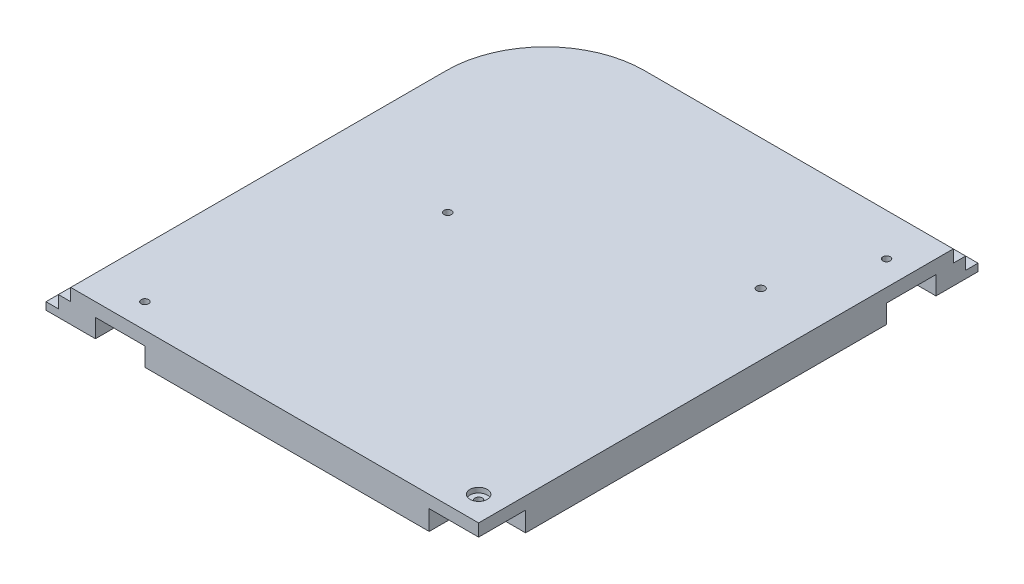
SolidWorks part; units mm, degrees
material "PETG"
ref_plane "Alzado" through (0, 0, 0) normal (0, 0, 1) x (1, 0, 0)
ref_plane "Planta" through (0, 0, 0) normal (0, 1, 0) x (1, 0, 0)
ref_plane "Vista lateral" through (0, 0, 0) normal (1, 0, 0) x (0, 0, -1)
sketch "Croquis1" plane through (0, 0, 0) normal (0, 1, 0) x (1, 0, 0)
  line L1 (125, 225) -> (-125, 225)
  line L2 (175, 175) -> (175, -175)
  line L3 (125, -225) -> (-125, -225)
  line L4 (-175, 175) -> (-175, -175)
  line L5 (175, 225) -> (-175, -225) construction
  line L6 (175, -225) -> (-175, 225) construction
  arc A0 (-125, -225) -> (-175, -175) centre (-125, -175) cw
  arc A1 (175, -175) -> (125, -225) centre (125, -175) cw
  arc A2 (125, 225) -> (175, 175) centre (125, 175) cw
  arc A3 (-125, 225) -> (-175, 175) centre (-125, 175) ccw
  point P0 (0, 0)
  dimension "D3" = 50
  dimension "D1" = 450
  dimension "D2" = 350
extrude "Saliente-Extruir1" add sketch "Croquis1" along normal blind 3
sketch "Croquis2" plane through (0, 3, 0) normal (0, 1, 0) x (1, 0, 0)
  line L8 (-125, -220) -> (125, -220)
  line L9 (170, -175) -> (170, 175)
  line L10 (125, 220) -> (-125, 220)
  line L11 (-170, 175) -> (-170, -175)
  line L12 (-125, -220) -> (125, -220)
  line L13 (170, -175) -> (170, 175)
  line L14 (125, 220) -> (-125, 220)
  line L15 (-170, 175) -> (-170, -175)
  arc A8 (-170, -175) -> (-125, -220) centre (-125, -175) ccw
  arc A9 (125, -220) -> (170, -175) centre (125, -175) ccw
  arc A10 (170, 175) -> (125, 220) centre (125, 175) ccw
  arc A11 (-125, 220) -> (-170, 175) centre (-125, 175) ccw
  arc A12 (-170, -175) -> (-125, -220) centre (-125, -175) ccw
  arc A13 (125, -220) -> (170, -175) centre (125, -175) ccw
  arc A14 (170, 175) -> (125, 220) centre (125, 175) ccw
  arc A15 (-125, 220) -> (-170, 175) centre (-125, 175) ccw
  dimension "D1" = 5
extrude "Saliente-Extruir2" add sketch "Croquis2" along normal blind 5
sketch "Croquis3" plane through (0, 8, 0) normal (0, 1, 0) x (1, 0, 0)
  line L8 (-125, -215) -> (125, -215)
  line L9 (165, -175) -> (165, 175)
  line L10 (125, 215) -> (-125, 215)
  line L11 (-165, 175) -> (-165, -175)
  line L12 (-125, -215) -> (125, -215)
  line L13 (165, -175) -> (165, 175)
  line L14 (125, 215) -> (-125, 215)
  line L15 (-165, 175) -> (-165, -175)
  arc A8 (-165, -175) -> (-125, -215) centre (-125, -175) ccw
  arc A9 (125, -215) -> (165, -175) centre (125, -175) ccw
  arc A10 (165, 175) -> (125, 215) centre (125, 175) ccw
  arc A11 (-125, 215) -> (-165, 175) centre (-125, 175) ccw
  arc A12 (-165, -175) -> (-125, -215) centre (-125, -175) ccw
  arc A13 (125, -215) -> (165, -175) centre (125, -175) ccw
  arc A14 (165, 175) -> (125, 215) centre (125, 175) ccw
  arc A15 (-125, 215) -> (-165, 175) centre (-125, 175) ccw
  dimension "D1" = 5
extrude "Saliente-Extruir3" add sketch "Croquis3" along normal blind 5
sketch "Croquis6" plane through (0, 13, 0) normal (0, 1, 0) x (1, 0, 0)
  line L0 (0, 0) -> (0, -215) construction
  line L1 (-125, -215) -> (125, -215) construction
  circle A0 centre (-87, -130) radius 2.25
  circle A1 centre (-87, -70) radius 2.25
  circle A2 centre (-87, -10) radius 2.25
  circle A3 centre (87, -130) radius 2.25
  circle A4 centre (87, -70) radius 2.25
  circle A5 centre (87, -10) radius 2.25
  dimension "D1" = 4.5
  dimension "D2" = 4.5
  dimension "D3" = 4.5
  dimension "D4" = 87
  dimension "D5" = 60
  dimension "D6" = 60
  dimension "D7" = 10
extrude "Cortar-Extruir3" cut sketch "Croquis6" against normal blind 5
sketch "Croquis7" plane through (0, 13, 0) normal (0, 1, 0) x (1, 0, 0)
  line L0 (0, -11.4875) -> (0, -220) construction
  line L1 (-125, -220) -> (125, -220) construction
  circle A0 centre (-115, -70) radius 1.5
  circle A1 centre (-115, 125.5) radius 1.5
  circle A2 centre (115, -70) radius 1.5
  circle A3 centre (115, 125.5) radius 1.5
  dimension "D1" = 3
  dimension "D2" = 3
  dimension "D3" = 115
  dimension "D4" = 70
  dimension "D5" = 125.5
  dimension "D6" = 115
extrude "Cortar-Extruir4" cut sketch "Croquis7" against normal through all
sketch "Croquis8" plane through (0, 13, 0) normal (0, 1, 0) x (1, 0, 0)
  line L0 (13.0147, -158) -> (13.0147, -178) construction
  line L4 (16.0147, -158) -> (16.0147, -178)
  line L5 (10.0147, -158) -> (10.0147, -178)
  line L6 (25.0147, -158) -> (25.0147, -178) construction
  line L7 (28.0147, -158) -> (28.0147, -178)
  line L8 (22.0147, -158) -> (22.0147, -178)
  line L9 (25.0147, -106) -> (25.0147, -126) construction
  line L10 (28.0147, -106) -> (28.0147, -126)
  line L11 (22.0147, -106) -> (22.0147, -126)
  line L12 (13.0147, -106) -> (13.0147, -126) construction
  line L15 (16.0147, -106) -> (16.0147, -126)
  line L16 (10.0147, -106) -> (10.0147, -126)
  arc A0 (10.0147, -168) -> (13.0147, -171) centre (13.0147, -168) ccw construction
  arc A1 (25.0147, -171) -> (28.0147, -168) centre (25.0147, -168) ccw construction
  arc A2 (16.0147, -116) -> (13.0147, -113) centre (13.0147, -116) ccw construction
  arc A3 (22.0147, -116) -> (25.0147, -119) centre (25.0147, -116) ccw construction
  arc A6 (16.0147, -158) -> (10.0147, -158) centre (13.0147, -158) ccw
  arc A7 (10.0147, -178) -> (16.0147, -178) centre (13.0147, -178) ccw
  arc A8 (28.0147, -158) -> (22.0147, -158) centre (25.0147, -158) ccw
  arc A9 (22.0147, -178) -> (28.0147, -178) centre (25.0147, -178) ccw
  arc A10 (28.0147, -106) -> (22.0147, -106) centre (25.0147, -106) ccw
  arc A11 (22.0147, -126) -> (28.0147, -126) centre (25.0147, -126) ccw
  arc A14 (16.0147, -106) -> (10.0147, -106) centre (13.0147, -106) ccw
  arc A15 (10.0147, -126) -> (16.0147, -126) centre (13.0147, -126) ccw
  arc A16 (13.0147, -113) -> (10.0147, -116) centre (13.0147, -116) ccw construction
  arc A17 (10.0147, -116) -> (13.0147, -119) centre (13.0147, -116) ccw construction
  arc A18 (13.0147, -119) -> (16.0147, -116) centre (13.0147, -116) ccw construction
  arc A19 (28.0147, -116) -> (25.0147, -113) centre (25.0147, -116) ccw construction
  arc A20 (25.0147, -119) -> (28.0147, -116) centre (25.0147, -116) ccw construction
  arc A21 (25.0147, -113) -> (22.0147, -116) centre (25.0147, -116) ccw construction
  arc A22 (25.0147, -165) -> (22.0147, -168) centre (25.0147, -168) ccw construction
  arc A23 (22.0147, -168) -> (25.0147, -171) centre (25.0147, -168) ccw construction
  arc A24 (28.0147, -168) -> (25.0147, -165) centre (25.0147, -168) ccw construction
  arc A25 (16.0147, -168) -> (13.0147, -165) centre (13.0147, -168) ccw construction
  arc A26 (13.0147, -171) -> (16.0147, -168) centre (13.0147, -168) ccw construction
  arc A27 (13.0147, -165) -> (10.0147, -168) centre (13.0147, -168) ccw construction
  point P10 (13.0147, -168)
  point P16 (25.0147, -168)
  point P23 (25.0147, -116)
  point P32 (13.0147, -116)
  dimension "D1" = 6
  dimension "D2" = 6
  dimension "D3" = 6
  dimension "D4" = 6
  dimension "D5" = 12
  dimension "D6" = 52
  dimension "D7" = 116
  dimension "D8" = 13.0147
  dimension "D9" = 20
  dimension "D10" = 20
  dimension "D11" = 20
  dimension "D12" = 20
extrude "Cortar-Extruir5" cut sketch "Croquis8" against normal blind 8
sketch "Croquis9" plane through (0, 13, 0) normal (0, 1, 0) x (1, 0, 0)
  circle A0 centre (13.0147, -168) radius 1.5
  circle A1 centre (25.0147, -168) radius 1.5
  circle A2 centre (13.0147, -116) radius 1.5
  circle A3 centre (25.0147, -116) radius 1.5
  circle A4 centre (-87, -70) radius 2.25 construction
  circle A5 centre (-87, -130) radius 1.5
  circle A6 centre (-87, -70) radius 1.5
  circle A7 centre (-87, -10) radius 1.5
  circle A8 centre (87, -10) radius 1.5
  circle A9 centre (87, -70) radius 1.5
  circle A10 centre (87, -130) radius 1.5
  dimension "D1" = 3
  dimension "D2" = 3
  dimension "D3" = 3
  dimension "D4" = 3
  dimension "D5" = 100.0147
  dimension "D6" = 112.0147
  dimension "D7" = 46
  dimension "D8" = 98
extrude "Cortar-Extruir6" cut sketch "Croquis9" against normal through all
sketch "Croquis10" plane through (0, 13, 0) normal (0, 1, 0) x (1, 0, 0)
  line L1 (50, -120) -> (75, -120)
  line L2 (50, -120) -> (50, -170)
  line L3 (50, -170) -> (75, -170)
  line L4 (75, -120) -> (75, -170)
  dimension "D1" = 50
  dimension "D2" = 25
  dimension "D3" = 120
  dimension "D4" = 50
extrude "Cortar-Extruir7" cut sketch "Croquis10" against normal blind 5
chamfer "Chaflán1" distance 5 angle 45 4 edges at (62.5, 13, 120) (50, 13, 145) (62.5, 13, 170) (75, 13, 145)
sketch "Croquis13" plane through (0, 13, 0) normal (0, 1, 0) x (1, 0, 0)
  circle A0 centre (-60, -50) radius 2.25
  circle A1 centre (-20, -50) radius 2.25
  circle A2 centre (-20, -90) radius 2.25
  circle A3 centre (-60, -90) radius 2.25
  circle A4 centre (-20, -50) radius 3.5
  circle A5 centre (-60, -50) radius 3.5
  circle A6 centre (-60, -90) radius 3.5
  circle A7 centre (-20, -90) radius 3.5
  dimension "D1" = 4.5
  dimension "D2" = 40
  dimension "D6" = 7
  dimension "D3" = 40
  dimension "D4" = 20
  dimension "D5" = 50
extrude "Saliente-Extruir4" add sketch "Croquis13" along normal blind 25
sketch "Croquis14" plane through (0, 13, 0) normal (0, 1, 0) x (1, 0, 0)
  circle A0 centre (3.15, -40) radius 1.25
  circle A1 centre (67.55, -40) radius 1.25
  circle A3 centre (67.55, -40) radius 3
  circle A4 centre (3.15, -40) radius 3
  circle A5 centre (3, -91.9) radius 3
  circle A6 centre (3, -91.9) radius 1.25
  circle A7 centre (67.4, -91.9) radius 3
  circle A8 centre (67.4, -91.9) radius 1.25
  circle A9 centre (-10, -102.9) radius 1.5
  circle A10 centre (-10, -102.9) radius 3
  circle A11 centre (-10, -118.1085) radius 3
  circle A12 centre (-10, -118.1085) radius 1.5
  dimension "D1" = 2.5
  dimension "D2" = 6
  dimension "D7" = 3
  dimension "D8" = 6
  dimension "D9" = 6
  dimension "D10" = 3
  dimension "D3" = 51.9
  dimension "D4" = 64.4
  dimension "D5" = 40
  dimension "D6" = 3
  dimension "D11" = 11
  dimension "D12" = 13
  dimension "D13" = 15.2085
  dimension "D14" = 64.4
  dimension "D15" = 0.15
extrude "Saliente-Extruir5" add sketch "Croquis14" along normal blind 10
sketch "Croquis12" plane through (0, 13, 0) normal (0, 1, 0) x (1, 0, 0)
  line L0 (-25.1, 12) -> (-25.1, 13.6) construction
  line L1 (-25.1, 12) -> (-23.5, 12) construction
  line L2 (25.1, 12) -> (23.5, 12) construction
  line L3 (25.1, 12) -> (25.1, 13.6) construction
  line L4 (25.1, 162.2) -> (25.1, 160.6) construction
  line L5 (25.1, 162.2) -> (23.5, 162.2) construction
  line L6 (-25.1, 162.2) -> (-23.5, 162.2) construction
  line L7 (-25.1, 162.2) -> (-25.1, 160.6) construction
  circle A0 centre (-25.1, 162.2) radius 1.6
  circle A1 centre (25.1, 162.2) radius 1.6
  circle A2 centre (-25.1, 12) radius 1.6
  circle A3 centre (25.1, 12) radius 1.6
  dimension "D4" = 3.2
  dimension "D1" = 12
  dimension "D2" = 47
  dimension "D3" = 23.5
  dimension "D5" = 147
  dimension "D6" = 147
extrude "Cortar-Extruir9" cut sketch "Croquis12" against normal through all
sketch "Croquis11" plane through (0, 0, 0) normal (0, -1, 0) x (1, 0, 0)
  line L0 (13.0147, 168) -> (25.0147, 168) construction
  line L1 (13.0147, 188) -> (25.0147, 188)
  line L2 (13.0147, 148) -> (25.0147, 148)
  line L3 (13.0147, 116) -> (25.0147, 116) construction
  line L4 (13.0147, 136) -> (25.0147, 136)
  line L5 (13.0147, 96) -> (25.0147, 96)
  circle A4 centre (87, 130) radius 6
  circle A5 centre (87, 70) radius 6
  circle A6 centre (87, 10) radius 6
  circle A7 centre (-87, 10) radius 6
  circle A8 centre (-87, 70) radius 6
  circle A9 centre (-87, 130) radius 6
  circle A10 centre (-115, 70) radius 6
  circle A11 centre (115, 70) radius 6
  circle A12 centre (115, -125.5) radius 6
  circle A15 centre (-115, -125.5) radius 6
  arc A16 (13.0147, 188) -> (13.0147, 148) centre (13.0147, 168) ccw
  arc A17 (25.0147, 148) -> (25.0147, 188) centre (25.0147, 168) ccw
  circle A18 centre (-25.1, -162.2) radius 6
  arc A19 (13.0147, 136) -> (13.0147, 96) centre (13.0147, 116) ccw
  arc A20 (25.0147, 96) -> (25.0147, 136) centre (25.0147, 116) ccw
  circle A21 centre (25.1, -162.2) radius 6
  circle A22 centre (-25.1, -12) radius 6
  circle A23 centre (25.1, -12) radius 6
  point P3 (19.0147, 168)
  point P10 (19.0147, 116)
  dimension "D1" = 12
  dimension "D2" = 20
  dimension "D3" = 20
extrude "Cortar-Extruir8" cut sketch "Croquis11" against normal blind 5
sketch "Croquis16" plane through (0, 0, 0) normal (1, 0, 0) x (0, 0, -1)
  line L0 (-175, 0) -> (175, 0) construction
  line L5 (-175, 8) -> (175, 8) construction
  line L6 (2, 8) -> (42, 8)
  line L7 (2, 8) -> (2, 0)
  line L8 (2, 0) -> (42, 0)
  line L9 (42, 8) -> (42, 0)
  dimension "D1" = 40
  dimension "D2" = 2
extrude "Cortar-Extruir10" cut sketch "Croquis16" against normal mid plane 40
sketch "Croquis17" plane through (0, 13, 0) normal (0, 1, 0) x (1, 0, 0)
  line L0 (-175, 23) -> (0, 23)
  line L2 (0, 23) -> (0, -225) construction
  line L3 (-125, -225) -> (125, -225) construction
  line L4 (-175, 175) -> (-175, -175) construction
  line L5 (-175, 23) -> (-175, 225) construction
  line L6 (-175, 225) -> (0, 225) construction
  line L7 (175, 225) -> (175, 23)
  line L8 (175, -225) -> (0, -225)
  line L9 (125, 225) -> (-125, 225) construction
  line L10 (175, -175) -> (175, 175) construction
  line L11 (0, 23) -> (175, 23) construction
  line L12 (-175, 23) -> (-175, -225)
  line L13 (-175, -225) -> (0, -225)
  line L14 (175, 23) -> (175, -225)
  line L15 (0, 23) -> (0, 225)
  line L16 (0, 225) -> (175, 225)
  point P20 (0, 0)
  dimension "D1" = 248
extrude "Cortar-Extruir11" cut sketch "Croquis17" against normal mid plane 60
sketch "Croquis19" plane through (0, 13, 0) normal (0, 1, 0) x (1, 0, 0)
  line L4 (0, 225) -> (-125, 225) construction
  line L5 (0, 215) -> (0, 23) construction
  line L6 (0, 23) -> (-165, 23) construction
  line L7 (-175, 175) -> (-175, 23) construction
  circle A0 centre (-10, 33) radius 1.5
  circle A1 centre (-10, 198) radius 1.5
  circle A2 centre (-145, 33) radius 1.5
  dimension "D1" = 3
  dimension "D2" = 3
  dimension "D3" = 3
  dimension "D4" = 27
  dimension "D5" = 10
  dimension "D6" = 10
  dimension "D7" = 30
  dimension "D8" = 10
extrude "Cortar-Extruir12" cut sketch "Croquis19" against normal blind 70
sketch "Croquis20" plane through (0, 0, 0) normal (1, 0, 0) x (0, 0, -1)
  line L5 (225, 0) -> (225, 3) construction
  line L6 (188, 7.5) -> (208, 7.5)
  line L7 (188, 7.5) -> (188, 0)
  line L8 (188, 0) -> (208, 0)
  line L9 (208, 7.5) -> (208, 0)
  line L11 (225, 0) -> (42, 0) construction
  dimension "D1" = 17
  dimension "D2" = 20
  dimension "D3" = 7.5
extrude "Cortar-Extruir13" cut sketch "Croquis20" against normal blind 20
sketch "Croquis21" plane through (0, 0, -23) normal (0, 0, 1) x (1, 0, 0)
  line L1 (-155, 7.5) -> (-135, 7.5)
  line L2 (-155, 7.5) -> (-155, 0)
  line L3 (-155, 0) -> (-135, 0)
  line L4 (-135, 7.5) -> (-135, 0)
  line L6 (-175, 0) -> (-175, 3) construction
  line L7 (-175, 0) -> (-20, 0) construction
  dimension "D1" = 7.5
  dimension "D2" = 20
  dimension "D3" = 20
extrude "Cortar-Extruir14" cut sketch "Croquis21" against normal blind 20
sketch "Croquis22" plane through (0, 0, 0) normal (0, -1, 0) x (1, 0, 0)
  line L22 (-27, -181) -> (-7, -181)
  line L23 (-27, -181) -> (-7, -181)
  line L24 (-27, -215) -> (-27, -181)
  line L25 (-27, -215) -> (-27, -181)
  line L26 (-162, -50) -> (-162, -30)
  line L27 (-162, -50) -> (-162, -30)
  line L28 (-27, -30) -> (-128, -30)
  line L29 (-162, -30) -> (-168, -30)
  line L30 (-168, -30) -> (-168, -175)
  line L31 (-125, -218) -> (-7, -218)
  line L32 (-7, -218) -> (-7, -215)
  line L33 (-27, -30) -> (-128, -30)
  line L34 (-128, -30) -> (-128, -50)
  line L35 (-128, -30) -> (-128, -50)
  line L36 (-128, -50) -> (-162, -50)
  line L37 (-7, -49) -> (-27, -49)
  line L38 (-27, -49) -> (-27, -30)
  line L39 (-128, -50) -> (-162, -50)
  line L40 (-7, -215) -> (-27, -215)
  line L41 (-7, -215) -> (-27, -215)
  line L43 (-162, -30) -> (-168, -30)
  line L44 (-168, -30) -> (-168, -175)
  line L45 (-125, -218) -> (-7, -218)
  line L46 (-7, -218) -> (-7, -215)
  line L51 (-7, -49) -> (-27, -49)
  line L52 (-27, -49) -> (-27, -30)
  line L56 (-7, -181) -> (-7, -49)
  line L57 (-7, -181) -> (-7, -49)
  arc A2 (-168, -175) -> (-125, -218) centre (-125, -175) ccw
  arc A3 (-168, -175) -> (-125, -218) centre (-125, -175) ccw
  circle A5 centre (-115, -125.5) radius 16
  circle A6 centre (-115, -125.5) radius 16
  circle A8 centre (-25.1, -162.2) radius 16
  circle A9 centre (-25.1, -162.2) radius 16
  point P7 (-22.7713, -178)
  dimension "D1" = 7
  dimension "D2" = 10
  dimension "D3" = 10
extrude "Cortar-Extruir15" cut sketch "Croquis22" against normal blind 6
sketch "Croquis23" plane through (0, 13, 0) normal (0, 1, 0) x (1, 0, 0)
  circle A2 centre (-10, 33) radius 3.5
  circle A3 centre (-10, 33) radius 3.5
  dimension "D1" = 2
extrude "Cortar-Extruir16" cut sketch "Croquis23" against normal blind 2
